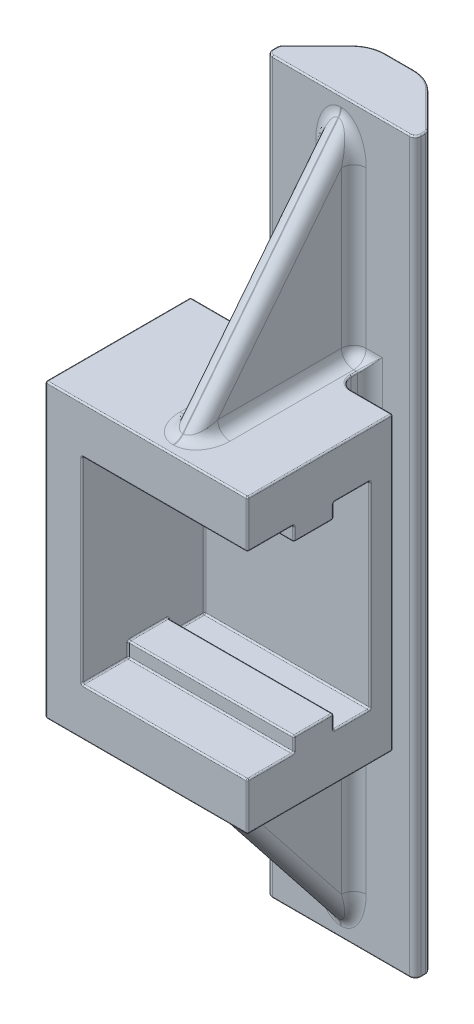
SolidWorks part; units mm, degrees
ref_plane "Front Plane" through (0, 0, 0) normal (0, 0, 1) x (1, 0, 0)
ref_plane "Top Plane" through (0, 0, 0) normal (0, 1, 0) x (1, 0, 0)
ref_plane "Right Plane" through (0, 0, 0) normal (1, 0, 0) x (0, 0, -1)
sketch "Sketch15" plane through (0, 0, 0) normal (0, 1, 0) x (1, 0, 0)
  line L0 (-3.964, 1.5536) -> (-3.964, 2.5104) construction
  line L1 (-5.6176, 4.164) -> (-9.3853, 4.164)
  line L2 (-10.187, 4.9657) -> (-10.187, 5.534)
  line L3 (-9.9522, 6.1008) -> (-5.2214, 10.8317)
  line L4 (-1.9335, 12.1936) -> (1.9335, 12.1936)
  line L5 (5.2214, 10.8317) -> (9.9522, 6.1008)
  line L6 (10.187, 5.534) -> (10.187, 4.9657)
  line L7 (9.3853, 4.164) -> (5.6176, 4.164)
  line L8 (3.964, 2.5104) -> (3.964, 1.5536) construction
  line L9 (-5.6176, 4.164) -> (5.6176, 4.164)
  line L130 (-14.3277, 0) -> (-9.4961, 0) construction
  line L131 (-7.9763, 0) -> (-5.6176, 0) construction
  line L132 (-4.064, 1.5536) -> (-4.064, 2.5104) construction
  line L133 (-5.6176, 4.064) -> (-9.3853, 4.064) construction
  line L134 (-10.287, 4.9657) -> (-10.287, 5.534) construction
  line L135 (-10.0229, 6.1716) -> (-5.2921, 10.9024) construction
  line L136 (-1.9335, 12.2936) -> (1.9335, 12.2936) construction
  line L137 (5.2921, 10.9024) -> (10.0229, 6.1716) construction
  line L138 (10.287, 5.534) -> (10.287, 4.9657) construction
  line L139 (9.3853, 4.064) -> (5.6176, 4.064) construction
  line L140 (4.064, 2.5104) -> (4.064, 1.5536) construction
  line L141 (5.6176, 0) -> (7.9763, 0) construction
  line L142 (9.4961, 0) -> (14.3277, 0) construction
  arc A0 (-5.6176, -0.1) -> (-3.964, 1.5536) centre (-5.6176, 1.5536) ccw construction
  arc A1 (-3.964, 2.5104) -> (-5.6176, 4.164) centre (-5.6176, 2.5104) ccw construction
  arc A2 (-10.187, 4.9657) -> (-9.3853, 4.164) centre (-9.3853, 4.9657) ccw
  arc A3 (-9.9522, 6.1008) -> (-10.187, 5.534) centre (-9.3853, 5.534) ccw
  arc A4 (-1.9335, 12.1936) -> (-5.2214, 10.8317) centre (-1.9335, 7.5438) ccw
  arc A5 (5.2214, 10.8317) -> (1.9335, 12.1936) centre (1.9335, 7.5438) ccw
  arc A6 (10.187, 5.534) -> (9.9522, 6.1008) centre (9.3853, 5.534) ccw
  arc A7 (9.3853, 4.164) -> (10.187, 4.9657) centre (9.3853, 4.9657) ccw
  arc A8 (5.6176, 4.164) -> (3.964, 2.5104) centre (5.6176, 2.5104) ccw construction
  arc A9 (3.964, 1.5536) -> (5.6176, -0.1) centre (5.6176, 1.5536) ccw construction
  arc A151 (-19.05, 3.2025) -> (-15.8475, 0) centre (-15.8751, 3.1749) ccw construction
  arc A152 (-14.3277, 0) -> (-15.8475, 0) centre (-15.0876, 0.0567) ccw construction
  arc A153 (-7.9763, 0) -> (-9.4961, 0) centre (-8.7362, 0.0567) ccw construction
  arc A154 (-5.6176, 0) -> (-4.064, 1.5536) centre (-5.6176, 1.5536) ccw construction
  arc A155 (-4.064, 2.5104) -> (-5.6176, 4.064) centre (-5.6176, 2.5104) ccw construction
  arc A156 (-10.287, 4.9657) -> (-9.3853, 4.064) centre (-9.3853, 4.9657) ccw construction
  arc A157 (-10.0229, 6.1716) -> (-10.287, 5.534) centre (-9.3853, 5.534) ccw construction
  arc A158 (-1.9335, 12.2936) -> (-5.2921, 10.9024) centre (-1.9335, 7.5438) ccw construction
  arc A159 (5.2921, 10.9024) -> (1.9335, 12.2936) centre (1.9335, 7.5438) ccw construction
  arc A160 (10.287, 5.534) -> (10.0229, 6.1716) centre (9.3853, 5.534) ccw construction
  arc A161 (9.3853, 4.064) -> (10.287, 4.9657) centre (9.3853, 4.9657) ccw construction
  arc A162 (5.6176, 4.064) -> (4.064, 2.5104) centre (5.6176, 2.5104) ccw construction
  arc A163 (4.064, 1.5536) -> (5.6176, 0) centre (5.6176, 1.5536) ccw construction
  arc A164 (9.4961, 0) -> (7.9763, 0) centre (8.7362, 0.0567) ccw construction
  point P0 (11.9119, 0)
  dimension "D1" = 0.1
extrude "Boss-Extrude6" add sketch "Sketch15" along normal mid plane 100
sketch "Sketch1" plane through (0, 0, 0) normal (0, 1, 0) x (1, 0, 0)
  line L5 (11.35, -0.1) -> (11.35, -20)
  line L6 (5.6176, -0.1) -> (8.093, -0.1) construction
  line L7 (-16.35, -20) -> (11.35, -20)
  line L8 (-5.6176, -0.1) -> (-3.964, -0.1)
  line L9 (-3.964, -0.1) -> (-3.964, 1.5536)
  line L10 (-3.964, 2.5104) -> (-3.964, 5)
  line L11 (3.964, 1.5536) -> (3.964, -0.1)
  line L12 (3.964, 2.5104) -> (3.964, 5)
  line L13 (3.964, -0.1) -> (5.6176, -0.1)
  line L14 (-14.3277, 0) -> (-9.4961, 0) construction
  line L15 (-14.4445, -0.1) -> (-16.35, -0.1)
  line L16 (5.6176, 0) -> (7.9763, 0) construction
  line L17 (4.064, 2.5104) -> (4.064, 1.5536) construction
  line L18 (9.3853, 4.064) -> (5.6176, 4.064) construction
  line L19 (-7.9763, 0) -> (-5.6176, 0) construction
  line L20 (-4.064, 1.5536) -> (-4.064, 2.5104) construction
  line L21 (-5.6176, 4.064) -> (-9.3853, 4.064) construction
  line L22 (-14.4445, -0.1) -> (-9.3794, -0.1)
  line L23 (-8.093, -0.1) -> (-5.6176, -0.1)
  line L24 (-3.964, 1.5536) -> (-3.964, 2.5104)
  line L26 (-16.35, -0.1) -> (-16.35, -20)
  line L27 (3.964, 2.5104) -> (3.964, 1.5536)
  line L28 (5.6176, -0.1) -> (11.35, -0.1)
  line L30 (9.3853, 4.164) -> (5.6176, 4.164) construction
  line L31 (-5.6176, 4.164) -> (-9.3853, 4.164) construction
  line L32 (3.964, 5) -> (-3.964, 5)
  line L35 (9.3794, -0.1) -> (14.4445, -0.1) construction
  line L36 (9.4961, 0) -> (14.3277, 0) construction
  arc A0 (-8.093, -0.1) -> (-9.3794, -0.1) centre (-8.7362, -0.1) ccw
  arc A10 (-19.05, 3.2025) -> (-15.8475, 0) centre (-15.8751, 3.1749) ccw construction
  arc A11 (-14.3277, 0) -> (-15.8475, 0) centre (-15.0876, 0.0567) ccw construction
  arc A12 (-7.9763, 0) -> (-9.4961, 0) centre (-8.7362, 0.0567) ccw construction
  arc A15 (9.4961, 0) -> (7.9763, 0) centre (8.7362, 0.0567) ccw construction
  arc A16 (4.064, 1.5536) -> (5.6176, 0) centre (5.6176, 1.5536) ccw construction
  arc A17 (5.6176, 4.064) -> (4.064, 2.5104) centre (5.6176, 2.5104) ccw construction
  arc A18 (-5.6176, 0) -> (-4.064, 1.5536) centre (-5.6176, 1.5536) ccw construction
  arc A19 (-4.064, 2.5104) -> (-5.6176, 4.064) centre (-5.6176, 2.5104) ccw construction
  arc A23 (-5.6176, -0.1) -> (-3.964, 1.5536) centre (-5.6176, 1.5536) ccw construction
  arc A24 (-3.964, 2.5104) -> (-5.6176, 4.164) centre (-5.6176, 2.5104) ccw construction
  arc A25 (5.6176, 4.164) -> (3.964, 2.5104) centre (5.6176, 2.5104) ccw construction
  arc A26 (3.964, 1.5536) -> (5.6176, -0.1) centre (5.6176, 1.5536) ccw construction
  arc A30 (15.7315, -0.097) -> (14.4445, -0.1) centre (15.0876, 0.0567) ccw construction
  arc A31 (15.7315, -0.097) -> (19.15, 3.2034) centre (15.8751, 3.1749) ccw construction
  arc A32 (15.8475, 0) -> (19.05, 3.2025) centre (15.8751, 3.1749) ccw construction
  arc A33 (15.8475, 0) -> (14.3277, 0) centre (15.0876, 0.0567) ccw construction
  arc A34 (-19.15, 3.2034) -> (-15.7315, -0.097) centre (-15.8751, 3.1749) ccw construction
  arc A35 (-14.4445, -0.1) -> (-15.7315, -0.097) centre (-15.0876, 0.0567) ccw construction
  arc A36 (-8.093, -0.1) -> (-9.3794, -0.1) centre (-8.7362, 0.0567) ccw construction
  arc A37 (9.3794, -0.1) -> (8.093, -0.1) centre (8.7362, 0.0567) ccw construction
  point P0 (0, 0)
  dimension "D1" = 5
  dimension "D2" = 20
  dimension "D4" = 11.35
  dimension "D5" = 16.35
  dimension "D3" = 0.1
extrude "Boss-Extrude1" add sketch "Sketch1" along normal mid plane 40
sketch "Sketch12" plane through (11.35, 0, 0) normal (1, 0, 0) x (0, 0, -1)
  line L0 (-22.65, 13.5) -> (-22.65, -13.5)
  line L2 (-22.65, 13.5) -> (-13.65, 13.5)
  line L3 (-13.65, 13.5) -> (-13.65, 11.5)
  line L4 (-13.65, 11.5) -> (-8.2, 11.5)
  line L5 (-8.2, 11.5) -> (-8.2, 13.5)
  line L6 (-8.2, 13.5) -> (-3.2, 13.5)
  line L7 (-3.2, 13.5) -> (-3.2, -13.5)
  line L8 (-3.2, -13.5) -> (-8.2, -13.5)
  line L9 (-8.2, -13.5) -> (-8.2, -11.5)
  line L10 (-8.2, -11.5) -> (-13.65, -11.5)
  line L11 (-13.65, -11.5) -> (-13.65, -13.5)
  line L12 (-13.65, -13.5) -> (-22.65, -13.5)
  line L13 (-0.1, 0) -> (-22.65, 0) construction
  line L14 (-0.1, 20) -> (-0.1, -20) construction
  point P5 (-22.65, 0)
  dimension "D1" = 27
  dimension "D2" = 9
  dimension "D3" = 5.45
  dimension "D4" = 5
  dimension "D5" = 2
  dimension "D6" = 3.2
extrude "Cut-Extrude4" cut sketch "Sketch12" against normal blind 22.7
sketch "Sketch16" plane through (0, 0, 0) normal (1, 0, 0) x (0, 0, -1)
  line L0 (4.164, 50) -> (4.164, -50) construction
  line L1 (-0.1, 20) -> (4.164, 20) construction
  line L2 (-20, 20) -> (-0.1, 20) construction
  line L3 (4.164, 50) -> (4.164, -50) construction
  line L4 (-0.1, 20) -> (4.164, 20) construction
  line L5 (-20, 20) -> (-0.1, 20) construction
  line L6 (-18, 20) -> (4.164, 48)
  dimension "D1" = 2
  dimension "D2" = 2
rib "Rib1" sketch "Sketch16" sketch "Sketch16" thickness 3.5 extrusion direction parallel to sketch draft on no parameters "D1"=3.5
mirror "Mirror1" about plane through (0, 0, 0) normal (0, 1, 0) of "Rib1"
fillet "Fillet1" radius 1.7 24 edges at (0, -20, 18) (0, -48, -4.164) (-1.75, 20, 6.918) (1.75, -34, 6.918) (1.75, -20, 6.918) (1.75, -34, -4.164) (-1.75, -34, 6.918) (-1.75, -34, -4.164) (-1.75, -20, 6.918) (2.857, -20, -4.164) (-2.857, -20, -4.164) (-1.75, 34, 6.918) (1.75, 34, 6.918) (0, 20, 18) (1.75, 34, -4.164) (1.75, 20, 6.918) (2.857, 20, -4.164) (3.964, 0, -4.164) (3.964, 0, 0.1) (-3.964, 0, 0.1) (0, 48, -4.164) (-1.75, 34, -4.164) (-2.857, 20, -4.164) (-3.964, 0, -4.164)
fillet "Fillet2" radius 0.2 91 edges at (-8.7362, 20, -0.5432) (-8.7362, -20, -0.5432) (8.507, 20, 0.1) (4.4619, 20, -0.3979) (3.964, 20, -2.032) (4.4619, -20.4979, -3.6661) (3.964, -20, -2.032) (8.507, -20, 0.1) (-4.4619, 20.4979, -3.6661) (-3.964, 20, -2.032) (-6.8785, 20, 0.1) (-4.4619, -20.4979, -3.6661) (-3.964, -20, -2.032) (-4.4619, -20, -0.3979) (-7.5868, -50, -8.4663) (-10.126, -50, -5.8408) (-10.187, -50, -5.2498) (-9.9522, -50, -4.3988) (0, -50, -4.164) (9.9522, -50, -4.3988) (10.187, -50, -5.2498) (10.126, -50, -5.8408) (7.5868, -50, -8.4663) (3.7129, -50, -11.8397) (0, -50, -12.1936) (-3.7129, -50, -11.8397) (3.7129, 50, -11.8397) (7.5868, 50, -8.4663) (10.126, 50, -5.8408) (10.187, 50, -5.2498) (9.9522, 50, -4.3988) (0, 50, -4.164) (-9.9522, 50, -4.3988) (-10.187, 50, -5.2498) (-10.126, 50, -5.8408) (-7.5868, 50, -8.4663) (-3.7129, 50, -11.8397) (0, 50, -12.1936) (-9.3794, 0, 0.1) (-12.8647, 20, 0.1) (-12.8647, -20, 0.1) (-2.5, -20, 20) (-2.5, 20, 20) (11.35, -12.5, 8.2) (11.35, 13.5, 5.7) (11.35, 12.5, 8.2) (11.35, 16.75, 20) (11.35, 20, 10.05) (11.35, 0, 0.1) (11.35, -20, 10.05) (11.35, -16.75, 20) (11.35, -12.5, 13.65) (0, -13.5, 20) (0, -13.5, 13.65) (11.35, -13.5, 16.825) (0, -11.5, 13.65) (0, -11.5, 8.2) (11.35, -11.5, 10.925) (0, -13.5, 8.2) (11.35, -13.5, 5.7) (0, -13.5, 3.2) (0, 13.5, 3.2) (11.35, 0, 3.2) (0, 11.5, 8.2) (11.35, 11.5, 10.925) (0, 11.5, 13.65) (11.35, 12.5, 13.65) (0, 13.5, 13.65) (0, 13.5, 20) (11.35, 13.5, 16.825) (-11.35, 0, 20) (-11.35, 13.5, 16.825) (-11.35, 12.5, 13.65) (-11.35, 11.5, 10.925) (-11.35, 12.5, 8.2) (-11.35, 13.5, 5.7) (-11.35, 0, 3.2) (-11.35, -13.5, 5.7) (-11.35, -12.5, 8.2) (-11.35, -11.5, 10.925) (-11.35, -12.5, 13.65) (-11.35, -13.5, 16.825) (4.4619, 20.4979, -3.6661) (4.4619, -20, -0.3979) (-4.4619, 20, -0.3979) (-6.8785, -20, 0.1) (0, 13.5, 8.2) (-16.35, 0, 0.1) (-16.35, 0, 20) (-16.35, 20, 10.05) (-16.35, -20, 10.05)
equation "\"D5@Sketch1\"=\"D4@Sketch1\"+5"
